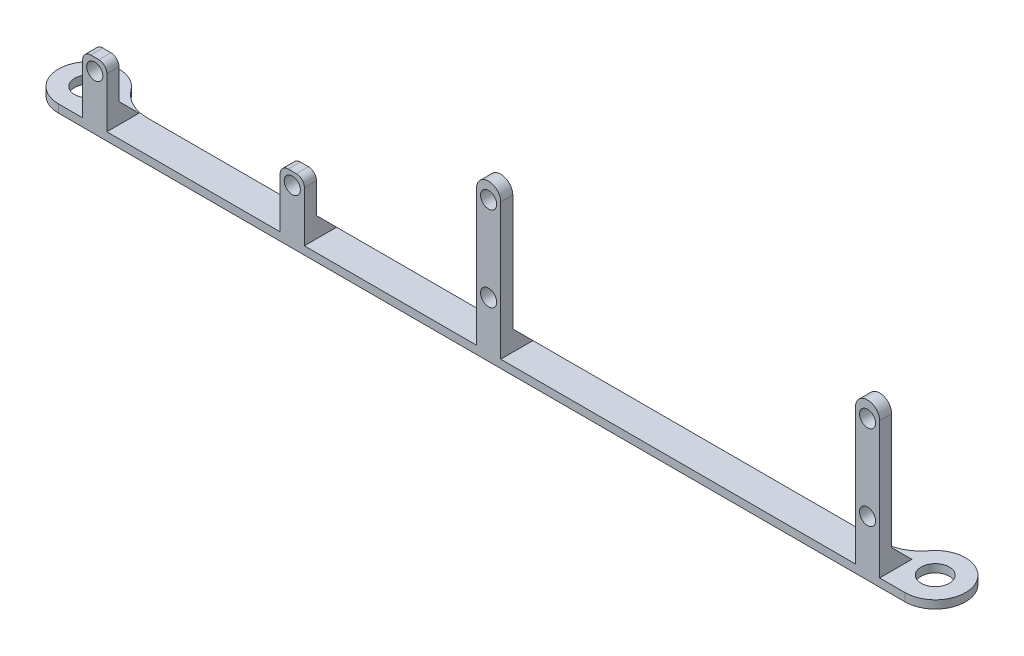
SolidWorks part; units mm, degrees
ref_plane "Front Plane" through (0, 0, 0) normal (0, 0, 1) x (1, 0, 0)
ref_plane "Top Plane" through (0, 0, 0) normal (0, 1, 0) x (1, 0, 0)
ref_plane "Right Plane" through (0, 0, 0) normal (1, 0, 0) x (0, 0, -1)
sketch "Sketch1" plane through (0, -82.5, 0) normal (0, 1, 0) x (1, 0, 0)
  line L0 (-105, 60) -> (105, 60) construction
  line L1 (-105, 67.5) -> (105, 67.5)
  line L2 (-105, 52.5) -> (105, 52.5)
  arc A0 (-105, 67.5) -> (-105, 52.5) centre (-105, 60) ccw
  arc A1 (105, 52.5) -> (105, 67.5) centre (105, 60) ccw
  circle A2 centre (-105, 60) radius 3.5
  circle A3 centre (105, 60) radius 3.5
  point P4 (0, 60)
  dimension "D2" = 7
  dimension "D1" = 15
extrude "Boss-Extrude1" add sketch "Sketch1" along normal blind 2
sketch "Sketch2" plane through (0, 0, -52.5) normal (0, 0, -1) x (-1, 0, 0)
  line L0 (-105, -80.5) -> (105, -80.5) construction
  line L1 (-98.705, -43.75) -> (-92.705, -43.75)
  line L2 (-98.705, -43.75) -> (-98.705, -80.5)
  line L3 (-98.705, -80.5) -> (-92.705, -80.5)
  line L4 (-92.705, -43.75) -> (-92.705, -80.5)
  line L6 (-4.705, -43.75) -> (1.295, -43.75)
  line L7 (-4.705, -43.75) -> (-4.705, -80.5)
  line L8 (-4.705, -80.5) -> (1.295, -80.5)
  line L9 (1.295, -43.75) -> (1.295, -80.5)
  line L10 (44.0035, -66) -> (50.0035, -66)
  line L11 (44.0035, -66) -> (44.0035, -80.5)
  line L12 (44.0035, -80.5) -> (50.0035, -80.5)
  line L13 (50.0035, -66) -> (50.0035, -80.5)
  line L14 (99.0035, -66) -> (93.0035, -66)
  line L15 (99.0035, -66) -> (99.0035, -80.5)
  line L16 (99.0035, -80.5) -> (93.0035, -80.5)
  line L17 (93.0035, -66) -> (93.0035, -80.5)
  circle A0 centre (-95.705, -47.75) radius 2
  circle A1 centre (-95.705, -68.75) radius 2
  circle A2 centre (-1.705, -47.75) radius 2
  circle A3 centre (-1.705, -68.75) radius 2
  circle A4 centre (47.0035, -69) radius 2
  circle A5 centre (96.0035, -69) radius 2
  point P36 (96.0035, -66)
  point P37 (47.0035, -66)
  point P38 (-1.705, -43.75)
  point P40 (-95.705, -43.75)
  dimension "D1" = 4
  dimension "D2" = 3
  dimension "D3" = 6
  dimension "D4" = 3
  dimension "D5" = 6
  dimension "D6" = 6
  dimension "D7" = 4
  dimension "D8" = 4
  dimension "D9" = 6
extrude "Boss-Extrude2" add sketch "Sketch2" along normal blind 3
fillet "Fillet1" 2 edges at (92.705, -43.75, -54) (98.705, -43.75, -54) type full round first side face at (92.705, -62.125, -54) second side face at (98.705, -62.125, -54) middle face at (95.705, -43.75, -54)
fillet "Fillet2" 2 edges at (-1.295, -43.75, -54) (4.705, -43.75, -54) type full round first side face at (-1.295, -62.125, -54) second side face at (4.705, -62.125, -54) middle face at (1.705, -43.75, -54)
fillet "Fillet3" radius 2 4 edges at (-93.0035, -66, -54) (-99.0035, -66, -54) (-44.0035, -66, -54) (-50.0035, -66, -54)
chamfer "Chamfer1" distance 5 angle 45 4 edges at (95.705, -80.5, -55.5) (1.705, -80.5, -55.5) (-47.0035, -80.5, -55.5) (-96.0035, -80.5, -55.5)
sketch "Sketch3" plane through (0, -80.5, 0) normal (0, 1, 0) x (1, 0, 0)
  line L0 (97.5167, 60.5) -> (-97.5167, 60.5)
  line L1 (-99.0035, 60.5) -> (-93.0035, 60.5) construction
  line L2 (105, 67.5) -> (-105, 67.5) construction
  line L3 (105, 67.5) -> (-105, 67.5)
  circle A0 centre (-105, 60) radius 7.5
  circle A1 centre (105, 60) radius 7.5
  line M4 (92.705, 60.5) -> (98.705, 60.5)
  line M8 (105, 67.5) -> (-105, 67.5)
  line M12 (-99.0035, 60.5) -> (-93.0035, 60.5)
  line M16 (-50.0035, 60.5) -> (-44.0035, 60.5)
  line M20 (-1.295, 60.5) -> (4.705, 60.5)
extrude "Cut-Extrude1" cut sketch "Sketch3" against normal blind 10 contours A1 A0 L0 M8 M12 M16 M20 M4 region at (0, -80.5, -64.0317)
fillet "Fillet4" radius 10 2 edges at (97.5167, -81.5, -60.5) (-97.5167, -81.5, -60.5)
equation "\"D4@Sketch2\"=\"D2@Sketch2\""
equation "\"D5@Sketch2\"=\"D3@Sketch2\""
equation "\"D8@Sketch2\"=\"D7@Sketch2\""
equation "\"D9@Sketch2\"=\"D6@Sketch2\""
